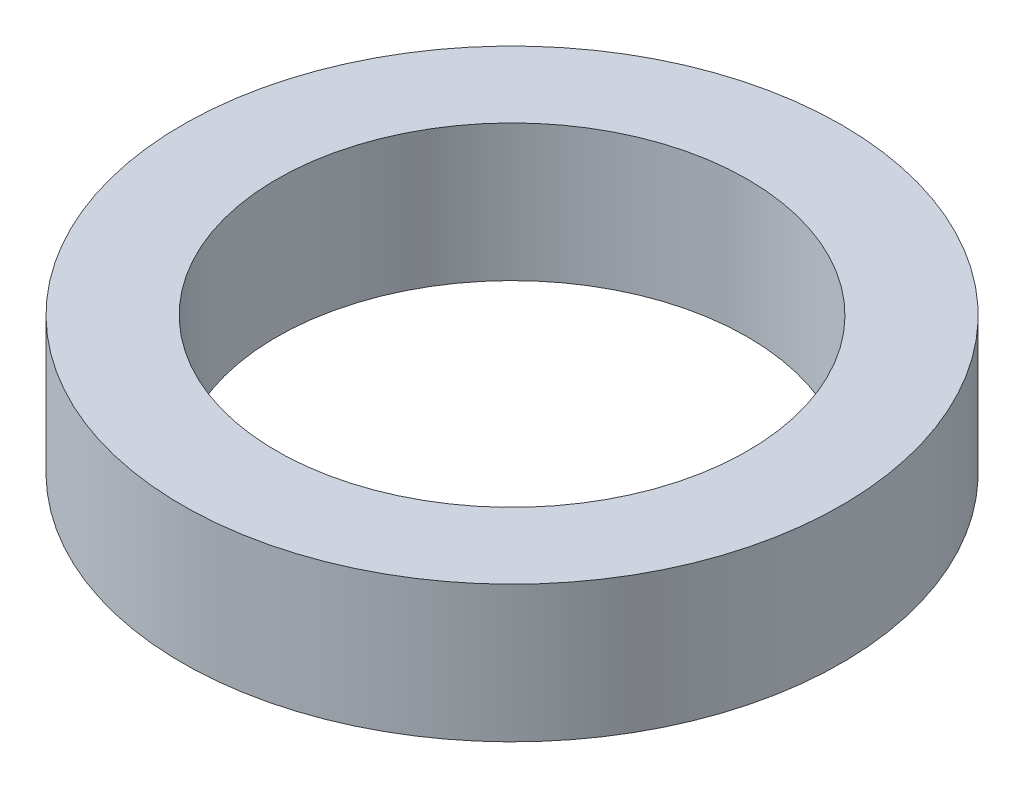
SolidWorks part; units mm, degrees
ref_plane "Front Plane" through (0, 0, 0) normal (0, 0, 1) x (1, 0, 0)
ref_plane "Top Plane" through (0, 0, 0) normal (0, 1, 0) x (1, 0, 0)
ref_plane "Right Plane" through (0, 0, 0) normal (1, 0, 0) x (0, 0, -1)
sketch "Sketch1" plane through (0, 0, 0) normal (0, 1, 0) x (1, 0, 0)
  circle A0 centre (0, 0) radius 70
  dimension "FLANGE_OD" = 140
extrude "Boss-Extrude1" add sketch "Sketch1" along normal blind 29
sketch "Sketch2" plane through (0, 0, 0) normal (0, 1, 0) x (1, 0, 0)
  circle A0 centre (0, 0) radius 50
  dimension "BORE_D" = 100
extrude "Cut-Extrude1" cut sketch "Sketch2" along normal through all
sketch "Sketch3" plane through (0, 29, 0) normal (0, 1, 0) x (1, 0, 0)
  circle A0 centre (0, 0) radius 29.6603 construction
  circle A1 centre (-29.6603, 0) radius 1.8665
  dimension "BOLT_D" = 3.733
  dimension "BOLT_PCD" = 59.3206
extrude "Cut-Extrude2" cut sketch "Sketch3" against normal blind 25.4494 rebuild error yes
pattern_circular "CirPattern1" count 5 over 360 rebuild error yes
